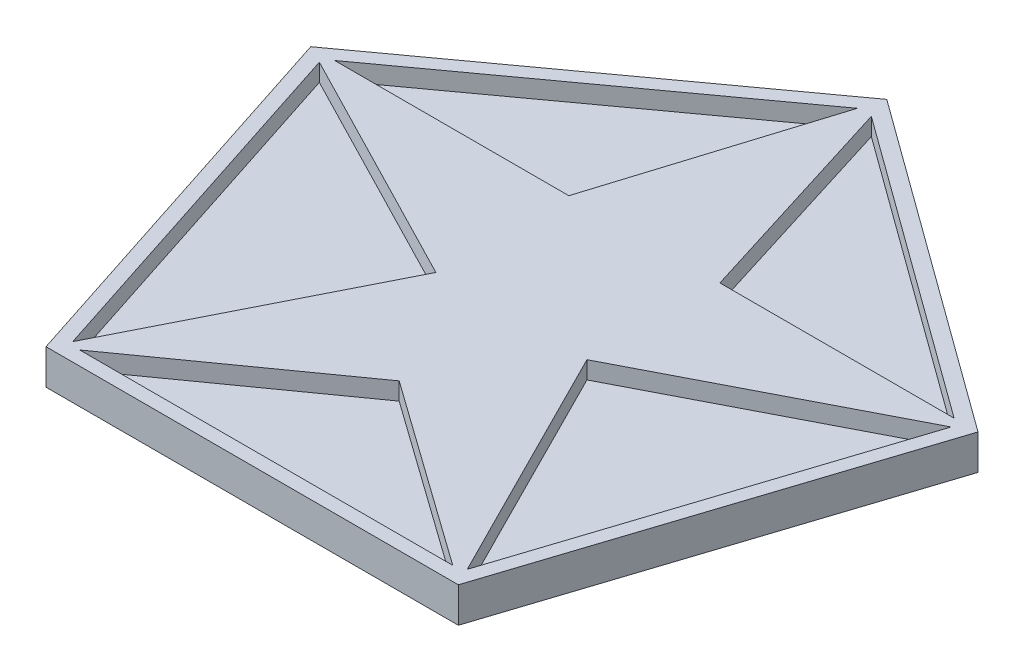
SolidWorks part; units mm, degrees
material "Pure Gold"
ref_plane "Front Plane" through (0, 0, 0) normal (0, 0, 1) x (1, 0, 0)
ref_plane "Top Plane" through (0, 0, 0) normal (0, 1, 0) x (1, 0, 0)
ref_plane "Right Plane" through (0, 0, 0) normal (1, 0, 0) x (0, 0, -1)
sketch "Sketch1" plane through (0, 0, 0) normal (0, 1, 0) x (1, 0, 0)
  line L11 (5.8779, -8.0902) -> (9.5106, 3.0902)
  line L12 (9.5106, 3.0902) -> (0, 10)
  line L13 (0, 10) -> (-9.5106, 3.0902)
  line L14 (-9.5106, 3.0902) -> (-5.8779, -8.0902)
  line L15 (-5.8779, -8.0902) -> (5.8779, -8.0902)
  line L20 (0, 3.0902) -> (0, -7.6902) construction
  line L21 (-5.3167, -7.6902) -> (5.3167, -7.6902)
  line L22 (5.4974, -7.9666) -> (9.1301, 3.2138) construction
  line L23 (-5.3167, -7.6902) -> (0, -3.9)
  line L24 (0, -3.9) -> (5.3167, -7.6902)
  line L25 (-8.83, 3.0902) -> (8.83, 3.0902) construction
  line L26 (5.6221, -7.5827) -> (2.1534, -0.6997)
  line L27 (2.1534, -0.6997) -> (9.0054, 2.83)
  line L28 (8.83, 3.0902) -> (2.1534, 3.0902)
  line L29 (2.1534, 3.0902) -> (0.1992, 9.3609)
  line L30 (-0.1992, 9.3609) -> (-2.1534, 3.0902)
  line L31 (-2.1534, 3.0902) -> (-8.83, 3.0902)
  line L32 (-9.0054, 2.83) -> (-2.1534, -0.6997)
  line L33 (-2.1534, -0.6997) -> (-5.6221, -7.5827)
  line L34 (-9.0054, 2.83) -> (-5.6221, -7.5827)
  line L35 (5.6221, -7.5827) -> (9.0054, 2.83)
  line L36 (-5.8779, -7.6902) -> (5.8779, -7.6902) construction
  line L37 (0.2351, 9.6764) -> (-9.0403, 2.9374) construction
  line L38 (-9.0403, 2.9374) -> (-5.4974, -7.9666) construction
  line L40 (-0.1992, 9.3609) -> (-8.83, 3.0902)
  line L41 (8.83, 3.0902) -> (0.1992, 9.3609)
  circle A0 centre (0, 0) radius 10 construction
  point P2 (0, 0)
  point P3 (0, 0)
  point P4 (0, 0)
  point P19 (0, 0)
  point P28 (0, 0)
  dimension "D1" = 20
  dimension "D3" = 3.9
  dimension "D2" = 0.4
extrude "Boss-Extrude1" add sketch "Sketch1" along normal blind 1
extrude "Boss-Extrude2" add sketch "Sketch1<2>" along normal blind 0.5 contours L26 L35 L27 | L28 L41 L29 | L30 L40 L31 | L32 L34 L33 | L24 L23 L21 region at (0, 0, 6.4268) region at (5.5937, 0, 1.8175) region at (3.7276, 0, -5.1804) region at (-3.7276, 0, -5.1804) region at (-5.5937, 0, 1.8175)
sketch "Sketch1<2>" plane through (0, 0, 0) normal (0, 1, 0) x (1, 0, 0) same geometry as "Sketch1"
